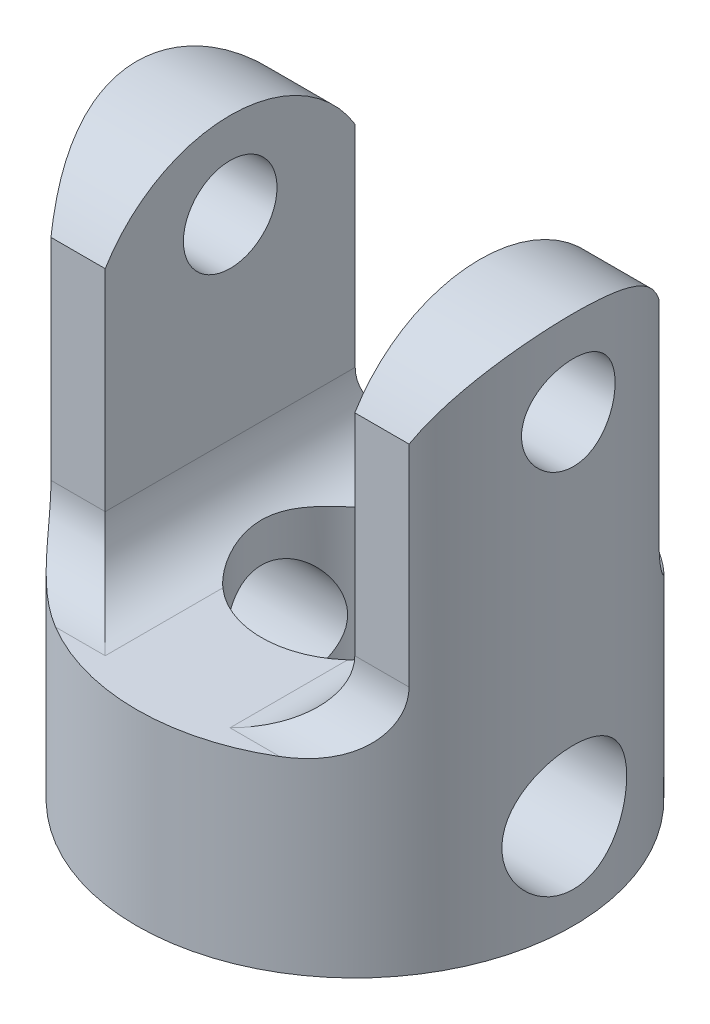
SolidWorks part; units mm, degrees
ref_plane "前视基准面" through (0, 0, 0) normal (0, 0, 1) x (1, 0, 0)
ref_plane "上视基准面" through (0, 0, 0) normal (0, 1, 0) x (1, 0, 0)
ref_plane "右视基准面" through (0, 0, 0) normal (1, 0, 0) x (0, 0, -1)
sketch "草图1" plane through (0, 0, 0) normal (0, 1, 0) x (1, 0, 0)
  circle A0 centre (0, 0) radius 3.5
extrude "凸台-拉伸1" add sketch "草图1" along normal blind 3
sketch "草图2" plane through (0, 0, 0) normal (0, -1, 0) x (1, 0, 0)
  circle A0 centre (0, 0) radius 1.5
extrude "切除-拉伸1" cut sketch "草图2" against normal blind 3
sketch "草图3" plane through (0, 0, 0) normal (1, 0, 0) x (0, 0, -1)
  circle A0 centre (0, 1.5065) radius 1
extrude "切除-拉伸2" cut sketch "草图3" against normal through all both and the other way through all
sketch "草图4" plane through (0, 3, 0) normal (0, 1, 0) x (1, 0, 0)
  line L0 (0, 0) -> (2.87, 0) construction
  line L1 (2.87, 2.0033) -> (2.87, -2.0033)
  circle A0 centre (0, 0) radius 3.5 construction
  arc A1 (2.87, 2.0033) -> (2.87, -2.0033) centre (0, 0) cw
extrude "凸台-拉伸2" add sketch "草图4" along normal blind 5.5
sketch "草图5" plane through (2.87, 0, 0) normal (-1, 0, 0) x (0, 0, 1)
  line L1 (-2.0033, 8.5) -> (-2.0033, 3) construction
  line L7 (-2.0033, 8.5) -> (0, 8.5)
  line L8 (-2.0033, 8.5) -> (-2.0033, 7.3726)
  arc A1 (-2.0033, 7.3726) -> (0, 8.5) centre (0, 6.1565) cw
  point P16 (0, 6.1565)
extrude "切除-拉伸11" cut sketch "草图5" against normal up to next
sketch "草图6" plane through (2.87, 0, 0) normal (-1, 0, 0) x (0, 0, 1)
  line L0 (2.0033, 8.5) -> (2.0033, 3) construction
  line L1 (0, 8.5) -> (2.0033, 8.5) construction
  line L2 (0, 8.5) -> (2.0033, 8.5)
  line L3 (2.0033, 8.5) -> (2.0033, 7.3726)
  arc A0 (2.0033, 7.3726) -> (0, 8.5) centre (0, 6.1565) ccw
extrude "切除-拉伸12" cut sketch "草图6" against normal up to next
sketch "草图7" plane through (2.87, 0, 0) normal (-1, 0, 0) x (0, 0, 1)
  line L0 (-2.0033, 7.3726) -> (-2.0033, 3)
  line L1 (-2.0033, 3) -> (2.0033, 3)
  line L2 (2.0033, 3) -> (2.0033, 7.3726)
  arc A0 (2.0033, 7.3726) -> (-2.0033, 7.3726) centre (0, 6.1565) ccw
extrude "凸台-拉伸3" add sketch "草图7" along normal blind 0.87
sketch "草图8" plane through (2, 0, 0) normal (-1, 0, 0) x (0, 0, 1)
  circle A0 centre (0, 7.1241) radius 0.75
extrude "切除-拉伸13" cut sketch "草图8" against normal up to next
mirror "镜向4" about plane through (0, 0, 0) normal (1, 0, 0) of "切除-拉伸13", "凸台-拉伸3", "切除-拉伸12", "切除-拉伸11", "凸台-拉伸2"
fillet "圆角29" radius 1 1 edges at (-2, 3, 0)
fillet "圆角30" radius 1 1 edges at (2, 3, 0)
fillet "圆角31" radius 1 2 edges at (-1.7071, 3.2929, -2.0033) (-1.935, 3, -2.0033)
fillet "圆角32" radius 1 2 edges at (1.7071, 3.2929, -2.0033) (1.935, 3, -2.0033)
fillet "圆角33" radius 1 2 edges at (1.7071, 3.2929, 2.0033) (1.935, 3, 2.0033)
fillet "圆角34" radius 1 2 edges at (-1.7071, 3.2929, 2.0033) (-1.935, 3, 2.0033)
